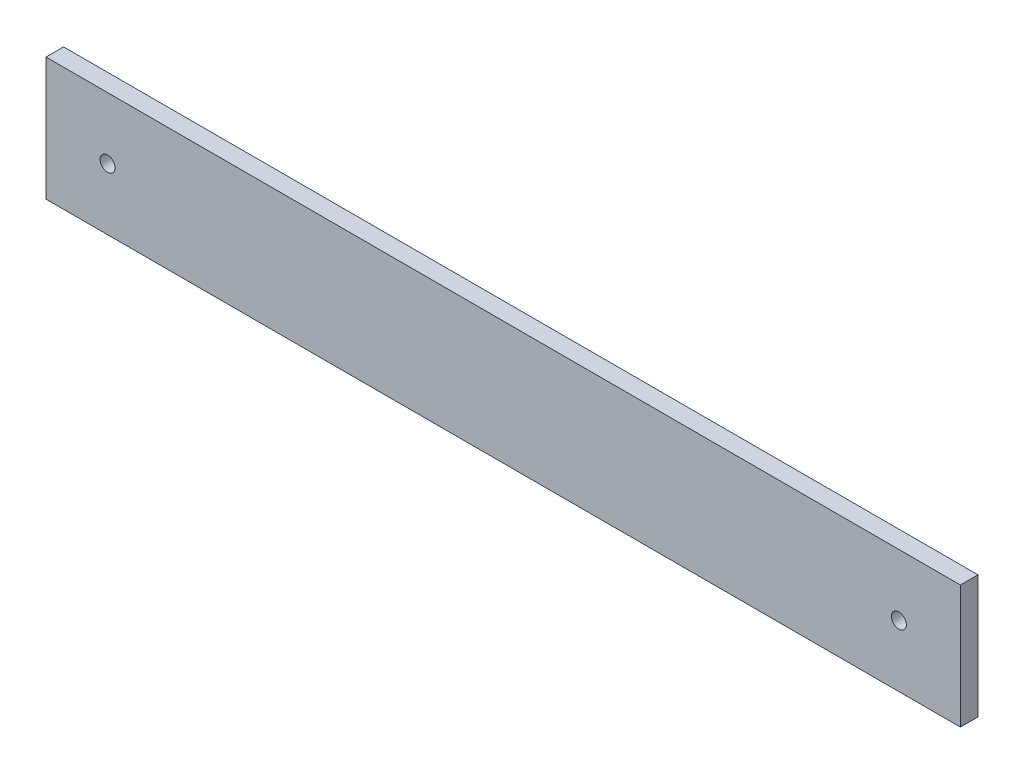
SolidWorks part; units mm, degrees
ref_plane "前视基准面" through (0, 0, 0) normal (0, 0, 1) x (1, 0, 0)
ref_plane "上视基准面" through (0, 0, 0) normal (0, 1, 0) x (1, 0, 0)
ref_plane "右视基准面" through (0, 0, 0) normal (1, 0, 0) x (0, 0, -1)
other "Configuration Table"
sketch "草图1" plane through (0, 0, 0) normal (0, 0, 1) x (1, 0, 0)
  line L1 (-14, -14) -> (194, -14)
  line L2 (-14, -14) -> (-14, 14)
  line L3 (-14, 14) -> (194, 14)
  line L4 (194, -14) -> (194, 14)
  line L5 (-14, -14) -> (194, 14) construction
  line L6 (-14, 14) -> (194, -14) construction
  circle A0 centre (0, 0) radius 1.7
  circle A1 centre (180, 0) radius 1.7
extrude "凸台-拉伸1" add sketch "草图1" along normal mid plane 4
